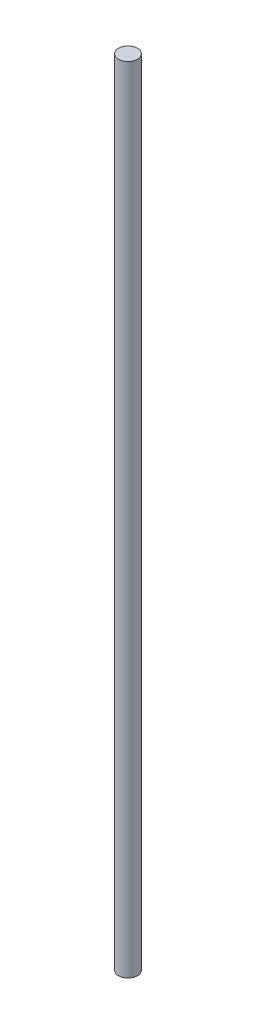
SolidWorks part; units mm, degrees
ref_plane "Front Plane" through (0, 0, 0) normal (0, 0, 1) x (1, 0, 0)
ref_plane "Top Plane" through (0, 0, 0) normal (0, 1, 0) x (1, 0, 0)
ref_plane "Right Plane" through (0, 0, 0) normal (1, 0, 0) x (0, 0, -1)
sketch "Sketch1" plane through (0, 0, 0) normal (0, 1, 0) x (1, 0, 0)
  circle A0 centre (0, 0) radius 3
  dimension "Diam" = 6
extrude "Boss-Extrude1" add sketch "Sketch1" along normal mid plane 250
